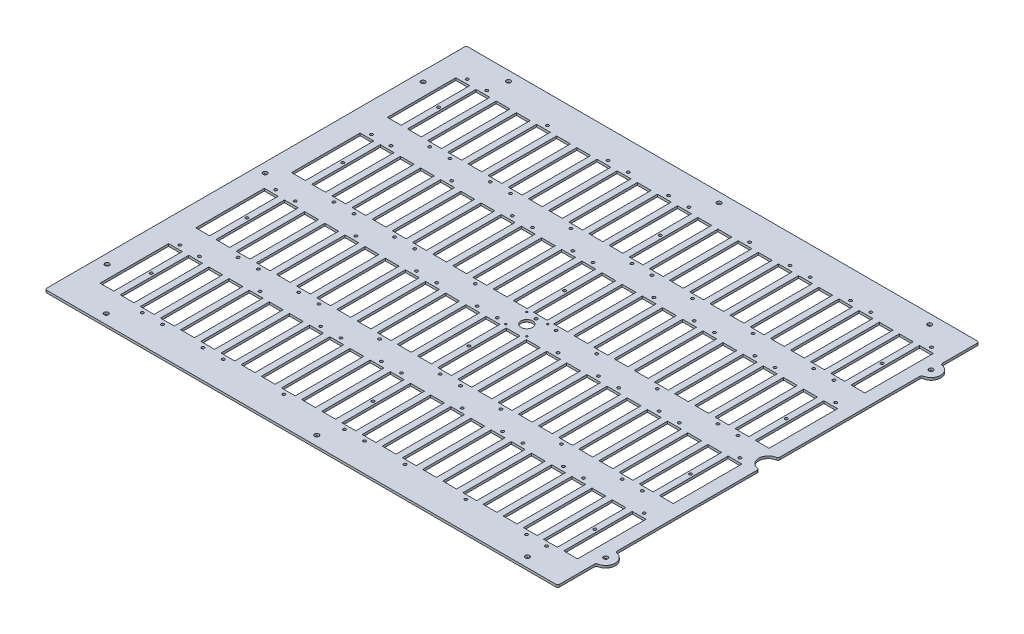
SolidWorks part; units mm, degrees
ref_plane "Front Plane" through (0, 0, 0) normal (0, 0, 1) x (1, 0, 0)
ref_plane "Top Plane" through (0, 0, 0) normal (0, 1, 0) x (1, 0, 0)
ref_plane "Right Plane" through (0, 0, 0) normal (1, 0, 0) x (0, 0, -1)
sketch "Sketch1" plane through (0, 0, 0) normal (0, 1, 0) x (1, 0, 0)
  line L0 (340.2584, 228.6) -> (340.2584, 279.5524)
  line L1 (-340.2584, -279.5524) -> (340.2584, -279.5524)
  line L2 (-340.2584, -279.5524) -> (-340.2584, 279.5524)
  line L3 (-340.2584, 279.5524) -> (340.2584, 279.5524)
  line L4 (340.2584, -279.5524) -> (340.2584, -228.6)
  line L5 (-340.2584, -279.5524) -> (340.2584, 279.5524) construction
  line L6 (-340.2584, 279.5524) -> (340.2584, -279.5524) construction
  line L7 (340.2584, 12.7) -> (340.2584, 203.2)
  line L8 (340.2584, -203.2) -> (340.2584, -12.7)
  arc A0 (340.2584, 203.2) -> (340.2584, 228.6) centre (340.2584, 215.9) ccw
  arc A1 (340.2584, -228.6) -> (340.2584, -203.2) centre (340.2584, -215.9) ccw
  arc A2 (340.2584, 12.7) -> (340.2584, -12.7) centre (340.2584, 0) ccw
  point P0 (0, 0)
  dimension "D3" = 25.4
  dimension "D4" = 63.6524
  dimension "D5" = 215.9
  dimension "D6" = 215.9
  dimension "D1" = 559.1048
  dimension "D2" = 680.5168
extrude "Boss-Extrude1" add sketch "Sketch1" along normal blind 3.175
sketch "Sketch17" plane through (0, 3.175, 0) normal (0, 1, 0) x (1, 0, 0)
  line L0 (340.2584, 279.5524) -> (-340.2584, 279.5524) construction
  line L1 (-314.8584, 254.1524) -> (327.5584, 254.1524) construction
  line L2 (-314.8584, 254.1524) -> (-314.8584, -254.1524) construction
  line L3 (-314.8584, -254.1524) -> (327.5584, -254.1524) construction
  line L4 (327.5584, 254.1524) -> (327.5584, -254.1524) construction
  line L5 (-340.2584, 279.5524) -> (-340.2584, -279.5524) construction
  line L6 (-340.2584, -279.5524) -> (340.2584, -279.5524) construction
  line L7 (340.2584, -203.2) -> (340.2584, -12.7) construction
  line L8 (-283.8406, 236.1184) -> (-265.5526, 236.1184)
  line L9 (-310.5912, 236.1184) -> (-292.3032, 236.1184)
  line L10 (-310.5912, 236.1184) -> (-310.5912, 145.1864)
  line L11 (-310.5912, 145.1864) -> (-292.3032, 145.1864)
  line L12 (-292.3032, 236.1184) -> (-292.3032, 145.1864)
  line L13 (-283.8406, 236.1184) -> (-283.8406, 145.1864)
  line L14 (-265.5526, 236.1184) -> (-265.5526, 145.1864)
  line L15 (-283.8406, 145.1864) -> (-265.5526, 145.1864)
  line L16 (-257.09, 236.1184) -> (-238.802, 236.1184)
  line L17 (-257.09, 236.1184) -> (-257.09, 145.1864)
  line L18 (-238.802, 236.1184) -> (-238.802, 145.1864)
  line L19 (-257.09, 145.1864) -> (-238.802, 145.1864)
  line L20 (-230.3393, 236.1184) -> (-212.0513, 236.1184)
  line L21 (-230.3393, 236.1184) -> (-230.3393, 145.1864)
  line L22 (-212.0513, 236.1184) -> (-212.0513, 145.1864)
  line L23 (-230.3393, 145.1864) -> (-212.0513, 145.1864)
  line L24 (-203.5887, 236.1184) -> (-185.3007, 236.1184)
  line L25 (-203.5887, 236.1184) -> (-203.5887, 145.1864)
  line L26 (-185.3007, 236.1184) -> (-185.3007, 145.1864)
  line L27 (-203.5887, 145.1864) -> (-185.3007, 145.1864)
  line L28 (-176.8381, 236.1184) -> (-158.5501, 236.1184)
  line L29 (-176.8381, 236.1184) -> (-176.8381, 145.1864)
  line L30 (-158.5501, 236.1184) -> (-158.5501, 145.1864)
  line L31 (-176.8381, 145.1864) -> (-158.5501, 145.1864)
  line L32 (-150.0875, 236.1184) -> (-131.7995, 236.1184)
  line L33 (-150.0875, 236.1184) -> (-150.0875, 145.1864)
  line L34 (-131.7995, 236.1184) -> (-131.7995, 145.1864)
  line L35 (-150.0875, 145.1864) -> (-131.7995, 145.1864)
  line L36 (-123.3369, 236.1184) -> (-105.0489, 236.1184)
  line L37 (-123.3369, 236.1184) -> (-123.3369, 145.1864)
  line L38 (-105.0489, 236.1184) -> (-105.0489, 145.1864)
  line L39 (-123.3369, 145.1864) -> (-105.0489, 145.1864)
  line L40 (-96.5863, 236.1184) -> (-78.2983, 236.1184)
  line L41 (-96.5863, 236.1184) -> (-96.5863, 145.1864)
  line L42 (-78.2983, 236.1184) -> (-78.2983, 145.1864)
  line L43 (-96.5863, 145.1864) -> (-78.2983, 145.1864)
  line L44 (-69.8356, 236.1184) -> (-51.5476, 236.1184)
  line L45 (-69.8356, 236.1184) -> (-69.8356, 145.1864)
  line L46 (-51.5476, 236.1184) -> (-51.5476, 145.1864)
  line L47 (-69.8356, 145.1864) -> (-51.5476, 145.1864)
  line L48 (-43.085, 236.1184) -> (-24.797, 236.1184)
  line L49 (-43.085, 236.1184) -> (-43.085, 145.1864)
  line L50 (-24.797, 236.1184) -> (-24.797, 145.1864)
  line L51 (-43.085, 145.1864) -> (-24.797, 145.1864)
  line L52 (-16.3344, 236.1184) -> (1.9536, 236.1184)
  line L53 (-16.3344, 236.1184) -> (-16.3344, 145.1864)
  line L54 (1.9536, 236.1184) -> (1.9536, 145.1864)
  line L55 (-16.3344, 145.1864) -> (1.9536, 145.1864)
  line L56 (10.4162, 236.1184) -> (28.7042, 236.1184)
  line L57 (10.4162, 236.1184) -> (10.4162, 145.1864)
  line L58 (28.7042, 236.1184) -> (28.7042, 145.1864)
  line L59 (10.4162, 145.1864) -> (28.7042, 145.1864)
  line L60 (37.1668, 236.1184) -> (55.4548, 236.1184)
  line L61 (37.1668, 236.1184) -> (37.1668, 145.1864)
  line L62 (55.4548, 236.1184) -> (55.4548, 145.1864)
  line L63 (37.1668, 145.1864) -> (55.4548, 145.1864)
  line L64 (63.9174, 236.1184) -> (82.2054, 236.1184)
  line L65 (63.9174, 236.1184) -> (63.9174, 145.1864)
  line L66 (82.2054, 236.1184) -> (82.2054, 145.1864)
  line L67 (63.9174, 145.1864) -> (82.2054, 145.1864)
  line L68 (90.6681, 236.1184) -> (108.9561, 236.1184)
  line L69 (90.6681, 236.1184) -> (90.6681, 145.1864)
  line L70 (108.9561, 236.1184) -> (108.9561, 145.1864)
  line L71 (90.6681, 145.1864) -> (108.9561, 145.1864)
  line L72 (117.4187, 236.1184) -> (135.7067, 236.1184)
  line L73 (117.4187, 236.1184) -> (117.4187, 145.1864)
  line L74 (135.7067, 236.1184) -> (135.7067, 145.1864)
  line L75 (117.4187, 145.1864) -> (135.7067, 145.1864)
  line L76 (144.1693, 236.1184) -> (162.4573, 236.1184)
  line L77 (144.1693, 236.1184) -> (144.1693, 145.1864)
  line L78 (162.4573, 236.1184) -> (162.4573, 145.1864)
  line L79 (144.1693, 145.1864) -> (162.4573, 145.1864)
  line L80 (170.9199, 236.1184) -> (189.2079, 236.1184)
  line L81 (170.9199, 236.1184) -> (170.9199, 145.1864)
  line L82 (189.2079, 236.1184) -> (189.2079, 145.1864)
  line L83 (170.9199, 145.1864) -> (189.2079, 145.1864)
  line L84 (197.6705, 236.1184) -> (215.9585, 236.1184)
  line L85 (197.6705, 236.1184) -> (197.6705, 145.1864)
  line L86 (215.9585, 236.1184) -> (215.9585, 145.1864)
  line L87 (197.6705, 145.1864) -> (215.9585, 145.1864)
  line L88 (224.4211, 236.1184) -> (242.7091, 236.1184)
  line L89 (224.4211, 236.1184) -> (224.4211, 145.1864)
  line L90 (242.7091, 236.1184) -> (242.7091, 145.1864)
  line L91 (224.4211, 145.1864) -> (242.7091, 145.1864)
  line L92 (251.1718, 236.1184) -> (269.4598, 236.1184)
  line L93 (251.1718, 236.1184) -> (251.1718, 145.1864)
  line L94 (269.4598, 236.1184) -> (269.4598, 145.1864)
  line L95 (251.1718, 145.1864) -> (269.4598, 145.1864)
  line L96 (277.9224, 236.1184) -> (296.2104, 236.1184)
  line L97 (277.9224, 236.1184) -> (277.9224, 145.1864)
  line L98 (296.2104, 236.1184) -> (296.2104, 145.1864)
  line L99 (277.9224, 145.1864) -> (296.2104, 145.1864)
  line L100 (304.673, 236.1184) -> (322.961, 236.1184)
  line L101 (304.673, 236.1184) -> (304.673, 145.1864)
  line L102 (322.961, 236.1184) -> (322.961, 145.1864)
  line L103 (304.673, 145.1864) -> (322.961, 145.1864)
  line L104 (-283.8406, 109.0422) -> (-265.5526, 109.0422)
  line L105 (-283.8406, 109.0422) -> (-283.8406, 18.1102)
  line L106 (-265.5526, 109.0422) -> (-265.5526, 18.1102)
  line L107 (-283.8406, 18.1102) -> (-265.5526, 18.1102)
  line L108 (-257.09, 109.0422) -> (-238.802, 109.0422)
  line L109 (-257.09, 109.0422) -> (-257.09, 18.1102)
  line L110 (-238.802, 109.0422) -> (-238.802, 18.1102)
  line L111 (-257.09, 18.1102) -> (-238.802, 18.1102)
  line L112 (-230.3393, 109.0422) -> (-212.0513, 109.0422)
  line L113 (-230.3393, 109.0422) -> (-230.3393, 18.1102)
  line L114 (-212.0513, 109.0422) -> (-212.0513, 18.1102)
  line L115 (-230.3393, 18.1102) -> (-212.0513, 18.1102)
  line L116 (-203.5887, 109.0422) -> (-185.3007, 109.0422)
  line L117 (-203.5887, 109.0422) -> (-203.5887, 18.1102)
  line L118 (-185.3007, 109.0422) -> (-185.3007, 18.1102)
  line L119 (-203.5887, 18.1102) -> (-185.3007, 18.1102)
  line L120 (-176.8381, 109.0422) -> (-158.5501, 109.0422)
  line L121 (-176.8381, 109.0422) -> (-176.8381, 18.1102)
  line L122 (-158.5501, 109.0422) -> (-158.5501, 18.1102)
  line L123 (-176.8381, 18.1102) -> (-158.5501, 18.1102)
  line L124 (-150.0875, 109.0422) -> (-131.7995, 109.0422)
  line L125 (-150.0875, 109.0422) -> (-150.0875, 18.1102)
  line L126 (-131.7995, 109.0422) -> (-131.7995, 18.1102)
  line L127 (-150.0875, 18.1102) -> (-131.7995, 18.1102)
  line L128 (-123.3369, 109.0422) -> (-105.0489, 109.0422)
  line L129 (-123.3369, 109.0422) -> (-123.3369, 18.1102)
  line L130 (-105.0489, 109.0422) -> (-105.0489, 18.1102)
  line L131 (-123.3369, 18.1102) -> (-105.0489, 18.1102)
  line L132 (-96.5863, 109.0422) -> (-78.2983, 109.0422)
  line L133 (-96.5863, 109.0422) -> (-96.5863, 18.1102)
  line L134 (-78.2983, 109.0422) -> (-78.2983, 18.1102)
  line L135 (-96.5863, 18.1102) -> (-78.2983, 18.1102)
  line L136 (-69.8356, 109.0422) -> (-51.5476, 109.0422)
  line L137 (-69.8356, 109.0422) -> (-69.8356, 18.1102)
  line L138 (-51.5476, 109.0422) -> (-51.5476, 18.1102)
  line L139 (-69.8356, 18.1102) -> (-51.5476, 18.1102)
  line L140 (-43.085, 109.0422) -> (-24.797, 109.0422)
  line L141 (-43.085, 109.0422) -> (-43.085, 18.1102)
  line L142 (-24.797, 109.0422) -> (-24.797, 18.1102)
  line L143 (-43.085, 18.1102) -> (-24.797, 18.1102)
  line L144 (-16.3344, 109.0422) -> (1.9536, 109.0422)
  line L145 (-16.3344, 109.0422) -> (-16.3344, 18.1102)
  line L146 (1.9536, 109.0422) -> (1.9536, 18.1102)
  line L147 (-16.3344, 18.1102) -> (1.9536, 18.1102)
  line L148 (10.4162, 109.0422) -> (28.7042, 109.0422)
  line L149 (10.4162, 109.0422) -> (10.4162, 18.1102)
  line L150 (28.7042, 109.0422) -> (28.7042, 18.1102)
  line L151 (10.4162, 18.1102) -> (28.7042, 18.1102)
  line L152 (37.1668, 109.0422) -> (55.4548, 109.0422)
  line L153 (37.1668, 109.0422) -> (37.1668, 18.1102)
  line L154 (55.4548, 109.0422) -> (55.4548, 18.1102)
  line L155 (37.1668, 18.1102) -> (55.4548, 18.1102)
  line L156 (63.9174, 109.0422) -> (82.2054, 109.0422)
  line L157 (63.9174, 109.0422) -> (63.9174, 18.1102)
  line L158 (82.2054, 109.0422) -> (82.2054, 18.1102)
  line L159 (63.9174, 18.1102) -> (82.2054, 18.1102)
  line L160 (90.6681, 109.0422) -> (108.9561, 109.0422)
  line L161 (90.6681, 109.0422) -> (90.6681, 18.1102)
  line L162 (108.9561, 109.0422) -> (108.9561, 18.1102)
  line L163 (90.6681, 18.1102) -> (108.9561, 18.1102)
  line L164 (117.4187, 109.0422) -> (135.7067, 109.0422)
  line L165 (117.4187, 109.0422) -> (117.4187, 18.1102)
  line L166 (135.7067, 109.0422) -> (135.7067, 18.1102)
  line L167 (117.4187, 18.1102) -> (135.7067, 18.1102)
  line L168 (144.1693, 109.0422) -> (162.4573, 109.0422)
  line L169 (144.1693, 109.0422) -> (144.1693, 18.1102)
  line L170 (162.4573, 109.0422) -> (162.4573, 18.1102)
  line L171 (144.1693, 18.1102) -> (162.4573, 18.1102)
  line L172 (170.9199, 109.0422) -> (189.2079, 109.0422)
  line L173 (170.9199, 109.0422) -> (170.9199, 18.1102)
  line L174 (189.2079, 109.0422) -> (189.2079, 18.1102)
  line L175 (170.9199, 18.1102) -> (189.2079, 18.1102)
  line L176 (197.6705, 109.0422) -> (215.9585, 109.0422)
  line L177 (197.6705, 109.0422) -> (197.6705, 18.1102)
  line L178 (215.9585, 109.0422) -> (215.9585, 18.1102)
  line L179 (197.6705, 18.1102) -> (215.9585, 18.1102)
  line L180 (224.4211, 109.0422) -> (242.7091, 109.0422)
  line L181 (224.4211, 109.0422) -> (224.4211, 18.1102)
  line L182 (242.7091, 109.0422) -> (242.7091, 18.1102)
  line L183 (224.4211, 18.1102) -> (242.7091, 18.1102)
  line L184 (251.1718, 109.0422) -> (269.4598, 109.0422)
  line L185 (251.1718, 109.0422) -> (251.1718, 18.1102)
  line L186 (269.4598, 109.0422) -> (269.4598, 18.1102)
  line L187 (251.1718, 18.1102) -> (269.4598, 18.1102)
  line L188 (277.9224, 109.0422) -> (296.2104, 109.0422)
  line L189 (277.9224, 109.0422) -> (277.9224, 18.1102)
  line L190 (296.2104, 109.0422) -> (296.2104, 18.1102)
  line L191 (277.9224, 18.1102) -> (296.2104, 18.1102)
  line L192 (304.673, 109.0422) -> (322.961, 109.0422)
  line L193 (304.673, 109.0422) -> (304.673, 18.1102)
  line L194 (322.961, 109.0422) -> (322.961, 18.1102)
  line L195 (304.673, 18.1102) -> (322.961, 18.1102)
  line L196 (-283.8406, -18.034) -> (-265.5526, -18.034)
  line L197 (-283.8406, -18.034) -> (-283.8406, -108.966)
  line L198 (-265.5526, -18.034) -> (-265.5526, -108.966)
  line L199 (-283.8406, -108.966) -> (-265.5526, -108.966)
  line L200 (-257.09, -18.034) -> (-238.802, -18.034)
  line L201 (-257.09, -18.034) -> (-257.09, -108.966)
  line L202 (-238.802, -18.034) -> (-238.802, -108.966)
  line L203 (-257.09, -108.966) -> (-238.802, -108.966)
  line L204 (-230.3393, -18.034) -> (-212.0513, -18.034)
  line L205 (-230.3393, -18.034) -> (-230.3393, -108.966)
  line L206 (-212.0513, -18.034) -> (-212.0513, -108.966)
  line L207 (-230.3393, -108.966) -> (-212.0513, -108.966)
  line L208 (-203.5887, -18.034) -> (-185.3007, -18.034)
  line L209 (-203.5887, -18.034) -> (-203.5887, -108.966)
  line L210 (-185.3007, -18.034) -> (-185.3007, -108.966)
  line L211 (-203.5887, -108.966) -> (-185.3007, -108.966)
  line L212 (-176.8381, -18.034) -> (-158.5501, -18.034)
  line L213 (-176.8381, -18.034) -> (-176.8381, -108.966)
  line L214 (-158.5501, -18.034) -> (-158.5501, -108.966)
  line L215 (-176.8381, -108.966) -> (-158.5501, -108.966)
  line L216 (-150.0875, -18.034) -> (-131.7995, -18.034)
  line L217 (-150.0875, -18.034) -> (-150.0875, -108.966)
  line L218 (-131.7995, -18.034) -> (-131.7995, -108.966)
  line L219 (-150.0875, -108.966) -> (-131.7995, -108.966)
  line L220 (-123.3369, -18.034) -> (-105.0489, -18.034)
  line L221 (-123.3369, -18.034) -> (-123.3369, -108.966)
  line L222 (-105.0489, -18.034) -> (-105.0489, -108.966)
  line L223 (-123.3369, -108.966) -> (-105.0489, -108.966)
  line L224 (-96.5863, -18.034) -> (-78.2983, -18.034)
  line L225 (-96.5863, -18.034) -> (-96.5863, -108.966)
  line L226 (-78.2983, -18.034) -> (-78.2983, -108.966)
  line L227 (-96.5863, -108.966) -> (-78.2983, -108.966)
  line L228 (-69.8356, -18.034) -> (-51.5476, -18.034)
  line L229 (-69.8356, -18.034) -> (-69.8356, -108.966)
  line L230 (-51.5476, -18.034) -> (-51.5476, -108.966)
  line L231 (-69.8356, -108.966) -> (-51.5476, -108.966)
  line L232 (-43.085, -18.034) -> (-24.797, -18.034)
  line L233 (-43.085, -18.034) -> (-43.085, -108.966)
  line L234 (-24.797, -18.034) -> (-24.797, -108.966)
  line L235 (-43.085, -108.966) -> (-24.797, -108.966)
  line L236 (-16.3344, -18.034) -> (1.9536, -18.034)
  line L237 (-16.3344, -18.034) -> (-16.3344, -108.966)
  line L238 (1.9536, -18.034) -> (1.9536, -108.966)
  line L239 (-16.3344, -108.966) -> (1.9536, -108.966)
  line L240 (10.4162, -18.034) -> (28.7042, -18.034)
  line L241 (10.4162, -18.034) -> (10.4162, -108.966)
  line L242 (28.7042, -18.034) -> (28.7042, -108.966)
  line L243 (10.4162, -108.966) -> (28.7042, -108.966)
  line L244 (37.1668, -18.034) -> (55.4548, -18.034)
  line L245 (37.1668, -18.034) -> (37.1668, -108.966)
  line L246 (55.4548, -18.034) -> (55.4548, -108.966)
  line L247 (37.1668, -108.966) -> (55.4548, -108.966)
  line L248 (63.9174, -18.034) -> (82.2054, -18.034)
  line L249 (63.9174, -18.034) -> (63.9174, -108.966)
  line L250 (82.2054, -18.034) -> (82.2054, -108.966)
  line L251 (63.9174, -108.966) -> (82.2054, -108.966)
  line L252 (90.6681, -18.034) -> (108.9561, -18.034)
  line L253 (90.6681, -18.034) -> (90.6681, -108.966)
  line L254 (108.9561, -18.034) -> (108.9561, -108.966)
  line L255 (90.6681, -108.966) -> (108.9561, -108.966)
  line L256 (117.4187, -18.034) -> (135.7067, -18.034)
  line L257 (117.4187, -18.034) -> (117.4187, -108.966)
  line L258 (135.7067, -18.034) -> (135.7067, -108.966)
  line L259 (117.4187, -108.966) -> (135.7067, -108.966)
  line L260 (144.1693, -18.034) -> (162.4573, -18.034)
  line L261 (144.1693, -18.034) -> (144.1693, -108.966)
  line L262 (162.4573, -18.034) -> (162.4573, -108.966)
  line L263 (144.1693, -108.966) -> (162.4573, -108.966)
  line L264 (170.9199, -18.034) -> (189.2079, -18.034)
  line L265 (170.9199, -18.034) -> (170.9199, -108.966)
  line L266 (189.2079, -18.034) -> (189.2079, -108.966)
  line L267 (170.9199, -108.966) -> (189.2079, -108.966)
  line L268 (197.6705, -18.034) -> (215.9585, -18.034)
  line L269 (197.6705, -18.034) -> (197.6705, -108.966)
  line L270 (215.9585, -18.034) -> (215.9585, -108.966)
  line L271 (197.6705, -108.966) -> (215.9585, -108.966)
  line L272 (224.4211, -18.034) -> (242.7091, -18.034)
  line L273 (224.4211, -18.034) -> (224.4211, -108.966)
  line L274 (242.7091, -18.034) -> (242.7091, -108.966)
  line L275 (224.4211, -108.966) -> (242.7091, -108.966)
  line L276 (251.1718, -18.034) -> (269.4598, -18.034)
  line L277 (251.1718, -18.034) -> (251.1718, -108.966)
  line L278 (269.4598, -18.034) -> (269.4598, -108.966)
  line L279 (251.1718, -108.966) -> (269.4598, -108.966)
  line L280 (277.9224, -18.034) -> (296.2104, -18.034)
  line L281 (277.9224, -18.034) -> (277.9224, -108.966)
  line L282 (296.2104, -18.034) -> (296.2104, -108.966)
  line L283 (277.9224, -108.966) -> (296.2104, -108.966)
  line L284 (304.673, -18.034) -> (322.961, -18.034)
  line L285 (304.673, -18.034) -> (304.673, -108.966)
  line L286 (322.961, -18.034) -> (322.961, -108.966)
  line L287 (304.673, -108.966) -> (322.961, -108.966)
  line L288 (-283.8406, -145.1102) -> (-265.5526, -145.1102)
  line L289 (-283.8406, -145.1102) -> (-283.8406, -236.0422)
  line L290 (-265.5526, -145.1102) -> (-265.5526, -236.0422)
  line L291 (-283.8406, -236.0422) -> (-265.5526, -236.0422)
  line L292 (-257.09, -145.1102) -> (-238.802, -145.1102)
  line L293 (-257.09, -145.1102) -> (-257.09, -236.0422)
  line L294 (-238.802, -145.1102) -> (-238.802, -236.0422)
  line L295 (-257.09, -236.0422) -> (-238.802, -236.0422)
  line L296 (-230.3393, -145.1102) -> (-212.0513, -145.1102)
  line L297 (-230.3393, -145.1102) -> (-230.3393, -236.0422)
  line L298 (-212.0513, -145.1102) -> (-212.0513, -236.0422)
  line L299 (-230.3393, -236.0422) -> (-212.0513, -236.0422)
  line L300 (-203.5887, -145.1102) -> (-185.3007, -145.1102)
  line L301 (-203.5887, -145.1102) -> (-203.5887, -236.0422)
  line L302 (-185.3007, -145.1102) -> (-185.3007, -236.0422)
  line L303 (-203.5887, -236.0422) -> (-185.3007, -236.0422)
  line L304 (-176.8381, -145.1102) -> (-158.5501, -145.1102)
  line L305 (-176.8381, -145.1102) -> (-176.8381, -236.0422)
  line L306 (-158.5501, -145.1102) -> (-158.5501, -236.0422)
  line L307 (-176.8381, -236.0422) -> (-158.5501, -236.0422)
  line L308 (-150.0875, -145.1102) -> (-131.7995, -145.1102)
  line L309 (-150.0875, -145.1102) -> (-150.0875, -236.0422)
  line L310 (-131.7995, -145.1102) -> (-131.7995, -236.0422)
  line L311 (-150.0875, -236.0422) -> (-131.7995, -236.0422)
  line L312 (-123.3369, -145.1102) -> (-105.0489, -145.1102)
  line L313 (-123.3369, -145.1102) -> (-123.3369, -236.0422)
  line L314 (-105.0489, -145.1102) -> (-105.0489, -236.0422)
  line L315 (-123.3369, -236.0422) -> (-105.0489, -236.0422)
  line L316 (-96.5863, -145.1102) -> (-78.2983, -145.1102)
  line L317 (-96.5863, -145.1102) -> (-96.5863, -236.0422)
  line L318 (-78.2983, -145.1102) -> (-78.2983, -236.0422)
  line L319 (-96.5863, -236.0422) -> (-78.2983, -236.0422)
  line L320 (-69.8356, -145.1102) -> (-51.5476, -145.1102)
  line L321 (-69.8356, -145.1102) -> (-69.8356, -236.0422)
  line L322 (-51.5476, -145.1102) -> (-51.5476, -236.0422)
  line L323 (-69.8356, -236.0422) -> (-51.5476, -236.0422)
  line L324 (-43.085, -145.1102) -> (-24.797, -145.1102)
  line L325 (-43.085, -145.1102) -> (-43.085, -236.0422)
  line L326 (-24.797, -145.1102) -> (-24.797, -236.0422)
  line L327 (-43.085, -236.0422) -> (-24.797, -236.0422)
  line L328 (-16.3344, -145.1102) -> (1.9536, -145.1102)
  line L329 (-16.3344, -145.1102) -> (-16.3344, -236.0422)
  line L330 (1.9536, -145.1102) -> (1.9536, -236.0422)
  line L331 (-16.3344, -236.0422) -> (1.9536, -236.0422)
  line L332 (10.4162, -145.1102) -> (28.7042, -145.1102)
  line L333 (10.4162, -145.1102) -> (10.4162, -236.0422)
  line L334 (28.7042, -145.1102) -> (28.7042, -236.0422)
  line L335 (10.4162, -236.0422) -> (28.7042, -236.0422)
  line L336 (37.1668, -145.1102) -> (55.4548, -145.1102)
  line L337 (37.1668, -145.1102) -> (37.1668, -236.0422)
  line L338 (55.4548, -145.1102) -> (55.4548, -236.0422)
  line L339 (37.1668, -236.0422) -> (55.4548, -236.0422)
  line L340 (63.9174, -145.1102) -> (82.2054, -145.1102)
  line L341 (63.9174, -145.1102) -> (63.9174, -236.0422)
  line L342 (82.2054, -145.1102) -> (82.2054, -236.0422)
  line L343 (63.9174, -236.0422) -> (82.2054, -236.0422)
  line L344 (90.6681, -145.1102) -> (108.9561, -145.1102)
  line L345 (90.6681, -145.1102) -> (90.6681, -236.0422)
  line L346 (108.9561, -145.1102) -> (108.9561, -236.0422)
  line L347 (90.6681, -236.0422) -> (108.9561, -236.0422)
  line L348 (117.4187, -145.1102) -> (135.7067, -145.1102)
  line L349 (117.4187, -145.1102) -> (117.4187, -236.0422)
  line L350 (135.7067, -145.1102) -> (135.7067, -236.0422)
  line L351 (117.4187, -236.0422) -> (135.7067, -236.0422)
  line L352 (144.1693, -145.1102) -> (162.4573, -145.1102)
  line L353 (144.1693, -145.1102) -> (144.1693, -236.0422)
  line L354 (162.4573, -145.1102) -> (162.4573, -236.0422)
  line L355 (144.1693, -236.0422) -> (162.4573, -236.0422)
  line L356 (170.9199, -145.1102) -> (189.2079, -145.1102)
  line L357 (170.9199, -145.1102) -> (170.9199, -236.0422)
  line L358 (189.2079, -145.1102) -> (189.2079, -236.0422)
  line L359 (170.9199, -236.0422) -> (189.2079, -236.0422)
  line L360 (197.6705, -145.1102) -> (215.9585, -145.1102)
  line L361 (197.6705, -145.1102) -> (197.6705, -236.0422)
  line L362 (215.9585, -145.1102) -> (215.9585, -236.0422)
  line L363 (197.6705, -236.0422) -> (215.9585, -236.0422)
  line L364 (224.4211, -145.1102) -> (242.7091, -145.1102)
  line L365 (224.4211, -145.1102) -> (224.4211, -236.0422)
  line L366 (242.7091, -145.1102) -> (242.7091, -236.0422)
  line L367 (224.4211, -236.0422) -> (242.7091, -236.0422)
  line L368 (251.1718, -145.1102) -> (269.4598, -145.1102)
  line L369 (251.1718, -145.1102) -> (251.1718, -236.0422)
  line L370 (269.4598, -145.1102) -> (269.4598, -236.0422)
  line L371 (251.1718, -236.0422) -> (269.4598, -236.0422)
  line L372 (277.9224, -145.1102) -> (296.2104, -145.1102)
  line L373 (277.9224, -145.1102) -> (277.9224, -236.0422)
  line L374 (296.2104, -145.1102) -> (296.2104, -236.0422)
  line L375 (277.9224, -236.0422) -> (296.2104, -236.0422)
  line L376 (304.673, -145.1102) -> (322.961, -145.1102)
  line L377 (304.673, -145.1102) -> (304.673, -236.0422)
  line L378 (322.961, -145.1102) -> (322.961, -236.0422)
  line L379 (304.673, -236.0422) -> (322.961, -236.0422)
  line L380 (-310.5912, 109.0422) -> (-292.3032, 109.0422)
  line L381 (-310.5912, 109.0422) -> (-310.5912, 18.1102)
  line L382 (-292.3032, 109.0422) -> (-292.3032, 18.1102)
  line L383 (-310.5912, 18.1102) -> (-292.3032, 18.1102)
  line L384 (-310.5912, -18.034) -> (-292.3032, -18.034)
  line L385 (-310.5912, -18.034) -> (-310.5912, -108.966)
  line L386 (-292.3032, -18.034) -> (-292.3032, -108.966)
  line L387 (-310.5912, -108.966) -> (-292.3032, -108.966)
  line L388 (-310.5912, -145.1102) -> (-292.3032, -145.1102)
  line L389 (-310.5912, -145.1102) -> (-310.5912, -236.0422)
  line L390 (-292.3032, -145.1102) -> (-292.3032, -236.0422)
  line L391 (-310.5912, -236.0422) -> (-292.3032, -236.0422)
  line L392 (340.2584, -279.5524) -> (340.2584, -228.6) construction
  dimension "D1" = 25.4
  dimension "D2" = 25.4
  dimension "D3" = 25.4
  dimension "D4" = 12.7
  dimension "D5" = 18.288
  dimension "D6" = 90.932
  dimension "D7" = 4.2672
  dimension "D8" = 18.034
  dimension "D9" = 508.3048
  dimension "D10" = 642.4168
  dimension "D11" = 24
  dimension "D13" = 17.2974
  dimension "D14" = 43.5102
  dimension "D12" = 4
extrude "Cut-Extrude5" cut sketch "Sketch17" against normal through all
hole_wizard "#25 (0.1495) Diameter Hole1" positions "Sketch18" profile "Sketch19" hole size "#25" standard "ANSI Inch" end condition through all
sketch "Sketch18" plane through (0, 3.175, 0) normal (0, 1, 0) x (1, 0, 0)
  line L1 (-301.4472, 145.1864) -> (-301.4472, 268.9262) construction
  line L2 (-310.5912, 145.1864) -> (-292.3032, 145.1864) construction
  line L3 (-292.3032, 236.1184) -> (-310.5912, 236.1184) construction
  line L4 (-301.4472, 241.9604) -> (316.2461, 241.9604) construction
  line L5 (-340.2584, 139.3444) -> (340.2584, 139.3444) construction
  line L6 (-340.2584, 279.5524) -> (-340.2584, -279.5524) construction
  line L7 (340.2584, 12.7) -> (340.2584, 203.2) construction
  line L9 (-283.8406, 145.1864) -> (-265.5526, 145.1864) construction
  point P9 (-301.4472, 241.9604)
  point P15 (-275.4503, 241.9604)
  point P17 (-194.9831, 241.9604)
  point P27 (-114.5159, 241.9604)
  point P29 (-87.6935, 241.9604)
  point P31 (-34.0487, 241.9604)
  point P33 (-7.2263, 241.9604)
  point P34 (73.2409, 241.9604)
  point P36 (126.8857, 241.9604)
  point P38 (153.7081, 241.9604)
  point P40 (207.3529, 241.9604)
  point P42 (234.1753, 241.9604)
  point P44 (314.6425, 241.9604)
  point P59 (-248.6279, 139.3444)
  point P61 (-221.8055, 139.3444)
  point P63 (-168.1607, 139.3444)
  point P65 (-141.3383, 139.3444)
  point P67 (-60.8711, 139.3444)
  point P69 (19.5961, 139.3444)
  point P71 (46.4185, 139.3444)
  point P73 (100.0633, 139.3444)
  point P75 (180.5305, 139.3444)
  point P77 (260.9977, 139.3444)
  point P79 (287.8201, 139.3444)
  point P88 (-301.4472, 114.8842)
  point P89 (-275.4503, 114.8842)
  point P90 (-194.9831, 114.8842)
  point P91 (-114.5159, 114.8842)
  point P92 (-87.6935, 114.8842)
  point P93 (-34.0487, 114.8842)
  point P94 (-7.2263, 114.8842)
  point P95 (73.2409, 114.8842)
  point P96 (126.8857, 114.8842)
  point P97 (153.7081, 114.8842)
  point P98 (207.3529, 114.8842)
  point P99 (234.1753, 114.8842)
  point P100 (314.6425, 114.8842)
  point P101 (-248.6279, 12.2682)
  point P102 (-221.8055, 12.2682)
  point P103 (-168.1607, 12.2682)
  point P104 (-141.3383, 12.2682)
  point P105 (-60.8711, 12.2682)
  point P106 (19.5961, 12.2682)
  point P107 (46.4185, 12.2682)
  point P108 (100.0633, 12.2682)
  point P109 (180.5305, 12.2682)
  point P110 (260.9977, 12.2682)
  point P111 (287.8201, 12.2682)
  point P112 (-301.4472, -12.192)
  point P113 (-275.4503, -12.192)
  point P114 (-194.9831, -12.192)
  point P115 (-114.5159, -12.192)
  point P116 (-87.6935, -12.192)
  point P117 (-34.0487, -12.192)
  point P118 (-7.2263, -12.192)
  point P119 (73.2409, -12.192)
  point P120 (126.8857, -12.192)
  point P121 (153.7081, -12.192)
  point P122 (207.3529, -12.192)
  point P123 (234.1753, -12.192)
  point P124 (314.6425, -12.192)
  point P125 (-248.6279, -114.808)
  point P126 (-221.8055, -114.808)
  point P127 (-168.1607, -114.808)
  point P128 (-141.3383, -114.808)
  point P129 (-60.8711, -114.808)
  point P130 (19.5961, -114.808)
  point P131 (46.4185, -114.808)
  point P132 (100.0633, -114.808)
  point P133 (180.5305, -114.808)
  point P134 (260.9977, -114.808)
  point P135 (287.8201, -114.808)
  point P136 (-301.4472, -139.2682)
  point P137 (-275.4503, -139.2682)
  point P138 (-194.9831, -139.2682)
  point P139 (-114.5159, -139.2682)
  point P140 (-87.6935, -139.2682)
  point P141 (-34.0487, -139.2682)
  point P142 (-7.2263, -139.2682)
  point P143 (73.2409, -139.2682)
  point P144 (126.8857, -139.2682)
  point P145 (153.7081, -139.2682)
  point P146 (207.3529, -139.2682)
  point P147 (234.1753, -139.2682)
  point P148 (314.6425, -139.2682)
  point P149 (-248.6279, -241.8842)
  point P150 (-221.8055, -241.8842)
  point P151 (-168.1607, -241.8842)
  point P152 (-141.3383, -241.8842)
  point P153 (-60.8711, -241.8842)
  point P154 (19.5961, -241.8842)
  point P155 (46.4185, -241.8842)
  point P156 (100.0633, -241.8842)
  point P157 (180.5305, -241.8842)
  point P158 (260.9977, -241.8842)
  point P159 (287.8201, -241.8842)
  dimension "D1" = 5.842
  dimension "D2" = 5.842
  dimension "D3" = 4
sketch "Sketch19" plane through (287.8201, 3.175, 241.8842) normal (1, 0, 0) x (0, 0, 1)
  line L0 (0, 0) -> (0, 3.175)
  line L1 (0, 3.175) -> (1.8986, 3.175)
  line L2 (1.8986, 3.175) -> (1.8986, 0)
  line L5 (1.8986, 0) -> (0, 0)
  line L11 (0, -6.35) -> (0, 107.95) construction
  dimension "Thru Hole Dia." = 3.7973
  dimension "Thru Hole Depth" = 3.175
fillet "Fillet1" radius 2.54 10 edges at (-340.2584, 1.5875, -279.5524) (-340.2584, 1.5875, 279.5524) (340.2584, 1.5875, 279.5524) (340.2584, 1.5875, 228.6) (340.2584, 1.5875, 203.2) (340.2584, 1.5875, 12.7) (340.2584, 1.5875, -12.7) (340.2584, 1.5875, -203.2) (340.2584, 1.5875, -279.5524) (340.2584, 1.5875, -228.6)
hole_wizard "#6 Clearance Hole1" positions "Sketch8" profile "Sketch9" hole size "#6" standard "ANSI Inch" end condition through all
sketch "Sketch8" plane through (0, 3.175, 0) normal (0, 1, 0) x (1, 0, 0)
  line L13 (-292.3032, 236.1184) -> (-283.8406, 145.1864) construction
  line L15 (1.9536, 236.1184) -> (10.4162, 145.1864) construction
  line L17 (296.2104, 236.1184) -> (304.673, 145.1864) construction
  line L18 (-292.3032, 109.0422) -> (-283.8406, 18.1102) construction
  line L19 (1.9536, 109.0422) -> (10.4162, 18.1102) construction
  line L20 (296.2104, 109.0422) -> (304.673, 18.1102) construction
  line L21 (-292.3032, -18.034) -> (-283.8406, -108.966) construction
  line L22 (1.9536, -18.034) -> (10.4162, -108.966) construction
  line L23 (296.2104, -18.034) -> (304.673, -108.966) construction
  line L24 (-292.3032, -145.1102) -> (-283.8406, -236.0422) construction
  line L25 (1.9536, -145.1102) -> (10.4162, -236.0422) construction
  line L26 (296.2104, -145.1102) -> (304.673, -236.0422) construction
  point P129 (-288.0719, 190.6524)
  point P131 (6.1849, 190.6524)
  point P133 (300.4417, 190.6524)
  point P146 (-288.0719, 63.5762)
  point P147 (6.1849, 63.5762)
  point P148 (300.4417, 63.5762)
  point P155 (-288.0719, -63.5)
  point P156 (6.1849, -63.5)
  point P157 (300.4417, -63.5)
  point P164 (-288.0719, -190.5762)
  point P165 (6.1849, -190.5762)
  point P166 (300.4417, -190.5762)
  dimension "D1" = 4
sketch "Sketch9" plane through (300.4417, 3.175, 190.5762) normal (1, 0, 0) x (0, 0, 1)
  line L0 (0, 0) -> (0, 3.175)
  line L1 (0, 3.175) -> (1.8986, 3.175)
  line L2 (1.8986, 3.175) -> (1.8986, 0)
  line L5 (1.8986, 0) -> (0, 0)
  line L11 (0, -6.35) -> (0, 107.95) construction
  dimension "Thru Hole Dia." = 3.7973
  dimension "Thru Hole Depth" = 3.175
hole_wizard "#2 Clearance Hole1" positions "Sketch13" profile "Sketch14" hole size "#2" standard "ANSI Inch" end condition through all
sketch "Sketch13" plane through (0, 3.175, 0) normal (0, 1, 0) x (1, 0, 0)
  line L9 (322.961, -108.966) -> (322.961, -18.034) construction
  line L10 (322.961, -18.034) -> (304.673, -18.034) construction
  line L18 (10.4162, 18.1102) -> (28.7042, -18.034) construction
  line L21 (5.6261, -13.9319) -> (33.5661, -13.9319) construction
  line L22 (5.6261, -13.9319) -> (5.6261, 14.0081) construction
  line L23 (5.6261, 14.0081) -> (33.5661, 14.0081) construction
  line L24 (33.5661, -13.9319) -> (33.5661, 14.0081) construction
  line L25 (5.6261, -13.9319) -> (33.5661, 14.0081) construction
  line L26 (5.6261, 14.0081) -> (33.5661, -13.9319) construction
  line L27 (10.4162, 18.1102) -> (28.7042, 18.1102) construction
  point P129 (5.6261, 14.0081)
  point P132 (5.6261, -13.9319)
  point P135 (33.5661, -13.9319)
  point P138 (33.5661, 14.0081)
  dimension "D1" = 27.94
  dimension "D2" = 27.94
  dimension "D3" = 4.1021
sketch "Sketch14" plane through (33.5661, 3.175, -14.0081) normal (1, 0, 0) x (0, 0, 1)
  line L0 (0, 0) -> (0, 3.175)
  line L1 (0, 3.175) -> (1.2192, 3.175)
  line L2 (1.2192, 3.175) -> (1.2192, 0)
  line L5 (1.2192, 0) -> (0, 0)
  line L11 (0, -6.35) -> (0, 107.95) construction
  dimension "Thru Hole Dia." = 2.4384
  dimension "Thru Hole Depth" = 3.175
sketch "Sketch20" plane through (0, 3.175, 0) normal (0, 1, 0) x (1, 0, 0)
  line L0 (5.6261, 14.0081) -> (33.5661, -13.9319) construction
  circle A0 centre (19.5961, 0.0381) radius 7.62
  dimension "D1" = 15.24
extrude "Cut-Extrude6" cut sketch "Sketch20" against normal through all
hole_wizard "#1 (0.228) Diameter Hole1" positions "Sketch21" profile "Sketch22" hole size "#1" standard "ANSI Inch" end condition through all
sketch "Sketch21" plane through (0, 3.175, 0) normal (0, 1, 0) x (1, 0, 0)
  point P0 (287.274, -266.8524)
  point P3 (340.2584, -215.9)
  point P6 (340.2584, 0)
  point P9 (340.2584, 215.9)
  point P12 (287.274, 266.8524)
  point P15 (7.874, 266.8524)
  point P18 (-271.526, 266.8524)
  point P21 (-327.5584, 209.55)
  point P24 (-327.5584, 0)
  point P27 (-327.5584, -209.55)
  point P30 (-271.526, -266.8524)
  point P33 (7.874, -266.8524)
sketch "Sketch22" plane through (287.274, 3.175, 266.8524) normal (1, 0, 0) x (0, 0, 1)
  line L0 (0, 0) -> (0, 3.175)
  line L1 (0, 3.175) -> (2.8956, 3.175)
  line L2 (2.8956, 3.175) -> (2.8956, 0)
  line L5 (2.8956, 0) -> (0, 0)
  line L11 (0, -6.35) -> (0, 107.95) construction
  dimension "Thru Hole Dia." = 5.7912
  dimension "Thru Hole Depth" = 3.175
